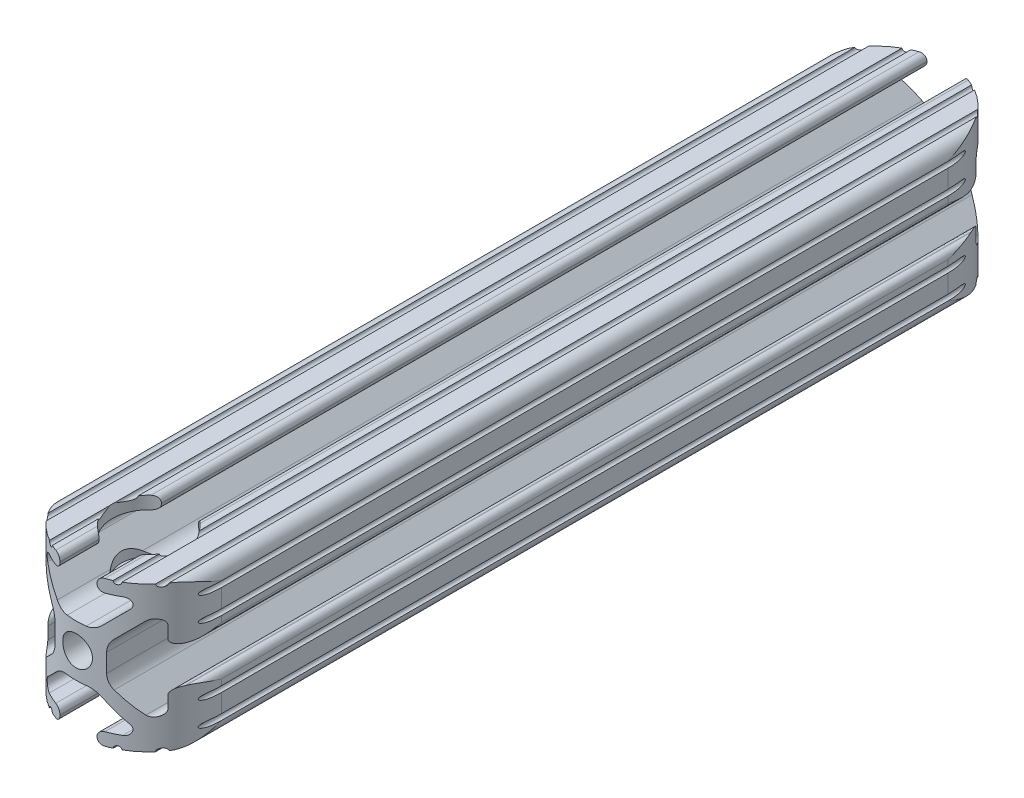
SolidWorks part; units mm, degrees
material "6061 Alloy"
ref_plane "Front Plane" through (0, 0, 0) normal (0, 0, 1) x (1, 0, 0)
ref_plane "Top Plane" through (0, 0, 0) normal (0, 1, 0) x (1, 0, 0)
ref_plane "Right Plane" through (0, 0, 0) normal (1, 0, 0) x (0, 0, -1)
sketch "Sketch1" plane through (0, 0, 0) normal (0, 0, 1) x (1, 0, 0)
  line L88 (-7.1797, -8.6452) -> (-3.9523, -5.4237)
  line L89 (-1.7093, -4.4958) -> (1.7093, -4.4958)
  line L90 (3.9523, -5.4237) -> (7.1797, -8.6452)
  line L91 (6.4164, -10.4902) -> (4.2875, -10.4902)
  line L92 (3.2385, -11.5392) -> (3.2385, -11.651)
  line L93 (4.2875, -12.7) -> (5.3171, -12.7)
  line L94 (6.3331, -12.7) -> (9.5504, -12.7)
  line L95 (12.7, -9.5504) -> (12.7, -6.3331)
  line L96 (12.7, -5.3171) -> (12.7, -4.2875)
  line L97 (11.651, -3.2385) -> (11.5392, -3.2385)
  line L98 (10.4902, -4.2875) -> (10.4902, -6.4021)
  line L99 (8.7371, -7.1294) -> (5.441, -3.8408)
  line L100 (4.5085, -1.5932) -> (4.5085, 1.5932)
  line L101 (5.441, 3.8408) -> (8.7371, 7.1294)
  line L102 (10.4902, 6.4021) -> (10.4902, 4.2875)
  line L103 (11.5392, 3.2385) -> (11.651, 3.2385)
  line L104 (12.7, 4.2875) -> (12.7, 5.3171)
  line L105 (12.7, 6.3331) -> (12.7, 9.5504)
  line L106 (9.5504, 12.7) -> (6.3331, 12.7)
  line L107 (5.3171, 12.7) -> (4.2875, 12.7)
  line L108 (3.2385, 11.651) -> (3.2385, 11.5392)
  line L109 (4.2875, 10.4902) -> (6.4768, 10.4902)
  line L110 (7.207, 8.7244) -> (3.8983, 5.4232)
  line L111 (1.6558, 4.4958) -> (-1.6558, 4.4958)
  line L112 (-3.8983, 5.4232) -> (-7.207, 8.7244)
  line L113 (-6.4768, 10.4902) -> (-4.2875, 10.4902)
  line L114 (-3.2385, 11.5392) -> (-3.2385, 11.651)
  line L115 (-4.2875, 12.7) -> (-5.3171, 12.7)
  line L116 (-6.3331, 12.7) -> (-9.5504, 12.7)
  line L117 (-12.7, 9.5504) -> (-12.7, 6.3331)
  line L118 (-12.7, 5.3171) -> (-12.7, 4.2875)
  line L119 (-11.651, 3.2385) -> (-11.5392, 3.2385)
  line L120 (-10.4902, 4.2875) -> (-10.4902, 6.4021)
  line L121 (-8.7371, 7.1294) -> (-5.441, 3.8408)
  line L122 (-4.5085, 1.5932) -> (-4.5085, -1.5932)
  line L123 (-5.441, -3.8408) -> (-8.7371, -7.1294)
  line L124 (-10.4902, -6.4021) -> (-10.4902, -4.2875)
  line L125 (-11.5392, -3.2385) -> (-11.651, -3.2385)
  line L126 (-12.7, -4.2875) -> (-12.7, -5.3171)
  line L127 (-12.7, -6.3331) -> (-12.7, -9.5504)
  line L128 (-9.5504, -12.7) -> (-6.3331, -12.7)
  line L129 (-5.3171, -12.7) -> (-4.2875, -12.7)
  line L130 (-3.2385, -11.651) -> (-3.2385, -11.5392)
  line L131 (-4.2875, -10.4902) -> (-6.4164, -10.4902)
  circle A1 centre (0, 0) radius 2.6035
  arc A104 (-7.1797, -8.6452) -> (-6.4164, -10.4902) centre (-6.4164, -9.4098) ccw
  arc A105 (-1.7093, -4.4958) -> (-3.9523, -5.4237) centre (-1.7093, -7.6708) ccw
  arc A106 (3.9523, -5.4237) -> (1.7093, -4.4958) centre (1.7093, -7.6708) ccw
  arc A107 (6.4164, -10.4902) -> (7.1797, -8.6452) centre (6.4164, -9.4098) ccw
  arc A108 (4.2875, -10.4902) -> (3.2385, -11.5392) centre (4.2875, -11.5392) ccw
  arc A109 (3.2385, -11.651) -> (4.2875, -12.7) centre (4.2875, -11.651) ccw
  arc A110 (6.3331, -12.7) -> (5.3171, -12.7) centre (5.8251, -12.7) ccw
  arc A111 (10.5664, -12.6998) -> (9.5504, -12.7) centre (10.0584, -12.7) ccw
  arc A112 (10.5664, -12.6998) -> (12.6998, -10.5664) centre (10.5918, -10.5918) ccw
  arc A113 (12.7, -9.5504) -> (12.6998, -10.5664) centre (12.7, -10.0584) ccw
  arc A114 (12.7, -5.3171) -> (12.7, -6.3331) centre (12.7, -5.8251) ccw
  arc A115 (12.7, -4.2875) -> (11.651, -3.2385) centre (11.651, -4.2875) ccw
  arc A116 (11.5392, -3.2385) -> (10.4902, -4.2875) centre (11.5392, -4.2875) ccw
  arc A117 (8.7371, -7.1294) -> (10.4902, -6.4021) centre (9.4628, -6.4021) ccw
  arc A118 (4.5085, -1.5932) -> (5.441, -3.8408) centre (7.6835, -1.5932) ccw
  arc A119 (5.441, 3.8408) -> (4.5085, 1.5932) centre (7.6835, 1.5932) ccw
  arc A120 (10.4902, 6.4021) -> (8.7371, 7.1294) centre (9.4628, 6.4021) ccw
  arc A121 (10.4902, 4.2875) -> (11.5392, 3.2385) centre (11.5392, 4.2875) ccw
  arc A122 (11.651, 3.2385) -> (12.7, 4.2875) centre (11.651, 4.2875) ccw
  arc A123 (12.7, 6.3331) -> (12.7, 5.3171) centre (12.7, 5.8251) ccw
  arc A124 (12.6998, 10.5664) -> (12.7, 9.5504) centre (12.7, 10.0584) ccw
  arc A125 (12.6998, 10.5664) -> (10.5664, 12.6998) centre (10.5918, 10.5918) ccw
  arc A126 (9.5504, 12.7) -> (10.5664, 12.6998) centre (10.0584, 12.7) ccw
  arc A127 (5.3171, 12.7) -> (6.3331, 12.7) centre (5.8251, 12.7) ccw
  arc A128 (4.2875, 12.7) -> (3.2385, 11.651) centre (4.2875, 11.651) ccw
  arc A129 (3.2385, 11.5392) -> (4.2875, 10.4902) centre (4.2875, 11.5392) ccw
  arc A130 (7.207, 8.7244) -> (6.4768, 10.4902) centre (6.4768, 9.4563) ccw
  arc A131 (1.6558, 4.4958) -> (3.8983, 5.4232) centre (1.6558, 7.6708) ccw
  arc A132 (-3.8983, 5.4232) -> (-1.6558, 4.4958) centre (-1.6558, 7.6708) ccw
  arc A133 (-6.4768, 10.4902) -> (-7.207, 8.7244) centre (-6.4768, 9.4563) ccw
  arc A134 (-4.2875, 10.4902) -> (-3.2385, 11.5392) centre (-4.2875, 11.5392) ccw
  arc A135 (-3.2385, 11.651) -> (-4.2875, 12.7) centre (-4.2875, 11.651) ccw
  arc A136 (-6.3331, 12.7) -> (-5.3171, 12.7) centre (-5.8251, 12.7) ccw
  arc A137 (-10.5664, 12.6998) -> (-9.5504, 12.7) centre (-10.0584, 12.7) ccw
  arc A138 (-10.5664, 12.6998) -> (-12.6998, 10.5664) centre (-10.5918, 10.5918) ccw
  arc A139 (-12.7, 9.5504) -> (-12.6998, 10.5664) centre (-12.7, 10.0584) ccw
  arc A140 (-12.7, 5.3171) -> (-12.7, 6.3331) centre (-12.7, 5.8251) ccw
  arc A141 (-12.7, 4.2875) -> (-11.651, 3.2385) centre (-11.651, 4.2875) ccw
  arc A142 (-11.5392, 3.2385) -> (-10.4902, 4.2875) centre (-11.5392, 4.2875) ccw
  arc A143 (-8.7371, 7.1294) -> (-10.4902, 6.4021) centre (-9.4628, 6.4021) ccw
  arc A144 (-4.5085, 1.5932) -> (-5.441, 3.8408) centre (-7.6835, 1.5932) ccw
  arc A145 (-5.441, -3.8408) -> (-4.5085, -1.5932) centre (-7.6835, -1.5932) ccw
  arc A146 (-10.4902, -6.4021) -> (-8.7371, -7.1294) centre (-9.4628, -6.4021) ccw
  arc A147 (-10.4902, -4.2875) -> (-11.5392, -3.2385) centre (-11.5392, -4.2875) ccw
  arc A148 (-11.651, -3.2385) -> (-12.7, -4.2875) centre (-11.651, -4.2875) ccw
  arc A149 (-12.7, -6.3331) -> (-12.7, -5.3171) centre (-12.7, -5.8251) ccw
  arc A150 (-12.6998, -10.5664) -> (-12.7, -9.5504) centre (-12.7, -10.0584) ccw
  arc A151 (-12.6998, -10.5664) -> (-10.5664, -12.6998) centre (-10.5918, -10.5918) ccw
  arc A152 (-9.5504, -12.7) -> (-10.5664, -12.6998) centre (-10.0584, -12.7) ccw
  arc A153 (-5.3171, -12.7) -> (-6.3331, -12.7) centre (-5.8251, -12.7) ccw
  arc A154 (-4.2875, -12.7) -> (-3.2385, -11.651) centre (-4.2875, -11.651) ccw
  arc A155 (-3.2385, -11.5392) -> (-4.2875, -10.4902) centre (-4.2875, -11.5392) ccw
extrude "Boss-Extrude1" add sketch "Sketch1" along normal mid plane 152.4
sketch "Sketch2" plane through (0, 12.7, 0) normal (0, 1, 0) x (1, 0, 0)
  line L0 (0, 76.2) -> (0, -76.2) construction
  line L1 (-12.7, 76.2) -> (12.7, 76.2)
  line L2 (-12.7, 76.2) -> (-12.7, -76.2)
  line L3 (-12.7, -76.2) -> (12.7, -76.2)
  line L4 (12.7, 76.2) -> (12.7, -76.2)
  circle A0 centre (0, 63.5) radius 12.7
  circle A1 centre (0, -63.5) radius 12.7
  circle A2 centre (0, -63.5) radius 3.175
  line M5 (-6.3331, 76.2) -> (-9.5504, 76.2)
  line M6 (-9.5504, 76.2) -> (-9.5504, -76.2)
  line M7 (-9.5504, -76.2) -> (-6.3331, -76.2)
  line M8 (-6.3331, -76.2) -> (-6.3331, 76.2)
  dimension "D1" = 6.35
extrude "Cut-Extrude1" cut sketch "Sketch2" against normal through all both and the other way through all contours A2 L0 | L0 A2 | A1 L2 L3 M6 | A1 M6 M7 M8 | A1 L3 M8 | A1 L3 L4 | A0 L4 L1 | A0 M8 M5 M6 | A0 L1 M8 | A0 L1 L2 M6 region at (-4.7717, 12.7, -75.6988) region at (9.8632, 12.7, -73.3632) region at (-8.1865, 12.7, -74.6688) region at (-11.3727, 12.7, -72.4456) region at (9.8632, 12.7, 73.3632) region at (1.3475, 12.7, 63.5) region at (-1.3475, 12.7, 63.5) region at (-4.7717, 12.7, 75.6988) region at (-8.1865, 12.7, 74.6688) region at (-11.3727, 12.7, 72.4456)
sketch "Sketch3" plane through (0, 12.7, 0) normal (0, 1, 0) x (1, 0, 0)
  circle A0 centre (0, -63.5) radius 6.35
  circle A1 centre (0, -63.5) radius 4.8006
  line M5 (6.3331, 74.5082) -> (6.3331, -74.5082)
  dimension "D1" = 12.7
  dimension "D2" = 9.6012
extrude "Cut-Extrude2" cut sketch "Sketch3" against normal up to vertex (8.2042 mm away) contours A1 | A0 A1 M5 region at (6.1536, 12.7, 63.5) region at (0, 12.7, 63.5) up to point (-7.207, 8.7244, 73.957)
extrude "Cut-Extrude4" cut sketch "Sketch3<3>" along normal blind 3.9756 from surface contours A1 | A0 A1 M5 region at (6.1536, 12.7, 63.5) region at (0, 12.7, 63.5) starting at face at (7.9961, -12.7, 0)
sketch "Sketch3<3>" plane through (0, 12.7, 0) normal (0, 1, 0) x (1, 0, 0) same geometry as "Sketch3"
extrude "Cut-Extrude5" cut sketch "Sketch3<5>" against normal up to surface (8.2042 mm away) contours A1 region at (0, 12.7, 63.5) up to face at (0, 4.4958, 71.2939)
sketch "Sketch3<5>" plane through (0, 12.7, 0) normal (0, 1, 0) x (1, 0, 0) same geometry as "Sketch3"
extrude "Cut-Extrude6" cut sketch "Sketch3<6>" along normal up to surface (8.2042 mm away) from surface contours A1 region at (0, 12.7, 63.5) up to face at (0, -4.4958, 71.2838) starting at face at (7.4418, -12.7, 21.1667)
sketch "Sketch3<6>" plane through (0, 12.7, 0) normal (0, 1, 0) x (1, 0, 0) same geometry as "Sketch3"
